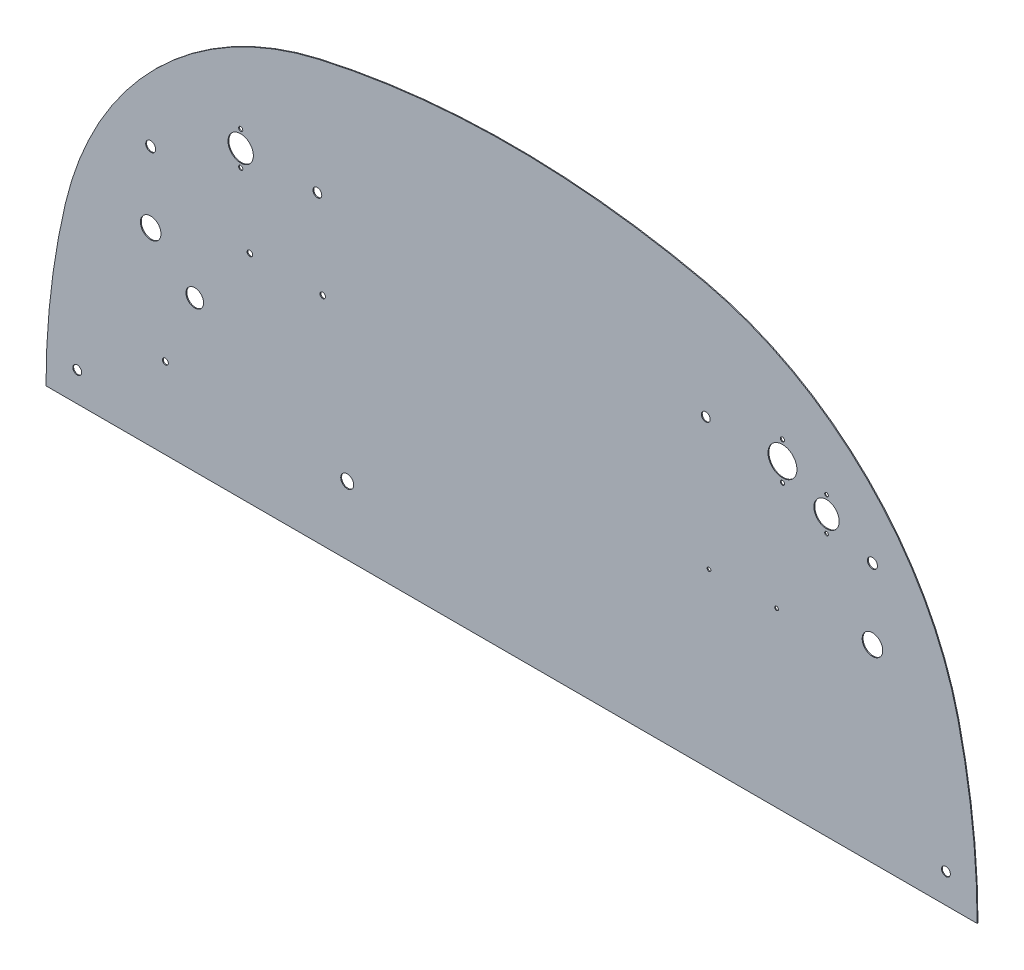
SolidWorks part; units mm, degrees
ref_plane "Front Plane" through (0, 0, 0) normal (0, 0, 1) x (1, 0, 0)
ref_plane "Top Plane" through (0, 0, 0) normal (0, 1, 0) x (1, 0, 0)
ref_plane "Right Plane" through (0, 0, 0) normal (1, 0, 0) x (0, 0, -1)
sketch "Base Sketch" plane through (0, 0, 0) normal (0, 0, 1) x (1, 0, 0)
  line L0 (0, 0) -> (750.8875, 0) construction
  line L1 (375.4437, 0) -> (375.4437, 236.5375) construction
  line L2 (543.3219, 236.5375) -> (207.5656, 236.5375) construction
  line L3 (-26.9875, -25.4) -> (777.875, -25.4)
  line L4 (375.4437, 0) -> (375.4437, -25.4) construction
  line L5 (375.4437, 236.5375) -> (375.4437, 355.6) construction
  line L6 (375.4437, 355.6) -> (-26.9875, 355.6) construction
  line L7 (-1.5875, -25.4) -> (375.4437, -25.4) construction
  line L8 (-1.5875, -25.4) -> (-1.5875, 152.4) construction
  line L9 (-1.5875, 152.4) -> (375.4437, 152.4) construction
  line L10 (375.4437, -25.4) -> (375.4437, 152.4) construction
  line L11 (23.8125, -25.4) -> (375.4437, -25.4) construction
  line L12 (23.8125, -25.4) -> (23.8125, 203.2) construction
  line L13 (23.8125, 203.2) -> (375.4437, 203.2) construction
  line L14 (375.4437, -25.4) -> (375.4437, 203.2) construction
  line L15 (49.2125, -25.4) -> (375.4437, -25.4) construction
  line L16 (49.2125, -25.4) -> (49.2125, 228.6) construction
  line L17 (49.2125, 228.6) -> (375.4437, 228.6) construction
  line L18 (375.4437, -25.4) -> (375.4437, 228.6) construction
  line L19 (74.6125, -25.4) -> (375.4437, -25.4) construction
  line L20 (74.6125, -25.4) -> (74.6125, 254) construction
  line L21 (74.6125, 254) -> (375.4437, 254) construction
  line L22 (375.4437, -25.4) -> (375.4437, 254) construction
  line L23 (100.0125, -25.4) -> (375.4437, -25.4) construction
  line L24 (100.0125, -25.4) -> (100.0125, 276.225) construction
  line L25 (100.0125, 276.225) -> (375.4437, 276.225) construction
  line L26 (375.4437, -25.4) -> (375.4437, 276.225) construction
  line L27 (125.4125, -25.4) -> (375.4437, -25.4) construction
  line L28 (125.4125, -25.4) -> (125.4125, 292.1) construction
  line L29 (125.4125, 292.1) -> (375.4437, 292.1) construction
  line L30 (375.4437, -25.4) -> (375.4437, 292.1) construction
  line L31 (150.8125, -25.4) -> (375.4437, -25.4) construction
  line L32 (150.8125, -25.4) -> (150.8125, 301.625) construction
  line L33 (150.8125, 301.625) -> (375.4437, 301.625) construction
  line L34 (375.4437, -25.4) -> (375.4437, 301.625) construction
  line L35 (176.2125, -25.4) -> (375.4437, -25.4) construction
  line L36 (176.2125, -25.4) -> (176.2125, 314.325) construction
  line L37 (176.2125, 314.325) -> (375.4437, 314.325) construction
  line L38 (375.4437, -25.4) -> (375.4437, 314.325) construction
  line L39 (201.6125, -25.4) -> (375.4437, -25.4) construction
  line L40 (201.6125, -25.4) -> (201.6125, 322.2625) construction
  line L41 (201.6125, 322.2625) -> (375.4437, 322.2625) construction
  line L42 (375.4437, -25.4) -> (375.4437, 322.2625) construction
  line L43 (227.0125, -25.4) -> (375.4437, -25.4) construction
  line L44 (227.0125, -25.4) -> (227.0125, 330.2) construction
  line L45 (227.0125, 330.2) -> (375.4437, 330.2) construction
  line L46 (375.4437, -25.4) -> (375.4437, 330.2) construction
  line L47 (252.4125, -25.4) -> (375.4437, -25.4) construction
  line L48 (252.4125, -25.4) -> (252.4125, 338.1375) construction
  line L49 (252.4125, 338.1375) -> (375.4437, 338.1375) construction
  line L50 (375.4437, -25.4) -> (375.4437, 338.1375) construction
  line L51 (277.8125, -25.4) -> (375.4437, -25.4) construction
  line L52 (277.8125, -25.4) -> (277.8125, 349.25) construction
  line L53 (277.8125, 349.25) -> (375.4437, 349.25) construction
  line L54 (375.4437, -25.4) -> (375.4437, 349.25) construction
  line L55 (-26.9875, -25.4) -> (-26.9875, 355.6) construction
  circle A0 centre (0, 0) radius 3.81
  circle A1 centre (750.8875, 0) radius 3.81
  circle A2 centre (207.5656, 236.5375) radius 3.81
  circle A3 centre (543.3219, 236.5375) radius 3.81
  arc A4 (-26.9875, -25.4) -> (777.875, -25.4) centre (375.4437, -47.434) cw construction
  arc A8 (-26.9875, -25.4) -> (-10.2771, 119.3168) centre (608.0125, -25.4) cw
  arc A9 (-10.2771, 119.3168) -> (208.9647, 336.9843) centre (273.2915, 52.9448) cw
  arc A10 (208.9647, 336.9843) -> (541.9228, 336.9843) centre (375.4437, -398.1152) cw
  arc A11 (761.1646, 119.3168) -> (541.9228, 336.9843) centre (477.596, 52.9448) ccw
  arc A12 (777.875, -25.4) -> (761.1646, 119.3168) centre (142.875, -25.4) ccw
  point P9 (375.4437, 236.5375)
  point P59 (0, 0)
  point P61 (0, 0)
  dimension "D1" = 7.62
  dimension "D2" = 750.8875
  dimension "D3" = 236.5375
  dimension "D4" = 335.7562
  dimension "D5" = 25.4
  dimension "D6" = 26.9875
  dimension "D8" = 25.4
  dimension "D9" = 177.8
  dimension "D10" = 50.8
  dimension "D11" = 228.6
  dimension "D12" = 76.2
  dimension "D13" = 254
  dimension "D14" = 101.6
  dimension "D15" = 279.4
  dimension "D16" = 127
  dimension "D17" = 301.625
  dimension "D18" = 152.4
  dimension "D19" = 317.5
  dimension "D20" = 177.8
  dimension "D21" = 327.025
  dimension "D22" = 203.2
  dimension "D23" = 339.725
  dimension "D24" = 228.6
  dimension "D25" = 347.6625
  dimension "D26" = 254
  dimension "D27" = 355.6
  dimension "D28" = 279.4
  dimension "D29" = 363.5375
  dimension "D30" = 304.8
  dimension "D31" = 374.65
extrude "Base w Mount Holes" add sketch "Base Sketch" along normal blind 0.7366
sketch "Throttle and Choke Cutout Sketch" plane through (0, 0, 0.7366) normal (0, 0, 1) x (1, 0, 0)
  line L0 (375.4438, -25.4) -> (375.4438, 355.6) construction
  line L2 (63.5, 199.0725) -> (63.5, 138.1125) construction
  line L3 (-26.9875, -25.4) -> (777.875, -25.4) construction
  line L4 (687.3875, 199.0725) -> (687.3875, 138.1125) construction
  circle A1 centre (63.5, 138.1125) radius 8.89
  circle A2 centre (63.5, 199.0725) radius 4.318
  arc A5 (541.9228, 336.9843) -> (208.9647, 336.9843) centre (375.4437, -398.1152) ccw construction
  circle A6 centre (687.3875, 199.0725) radius 4.318
  circle A7 centre (687.3875, 138.1125) radius 8.89
  point P11 (0, 0)
  dimension "D1" = 17.78
  dimension "D2" = 8.636
  dimension "D3" = 63.5
  dimension "D4" = 138.1125
  dimension "D5" = 199.0725
extrude "Throttle and Choke Cutouts" cut sketch "Throttle and Choke Cutout Sketch" against normal through all
sketch "Starter Relay Mount Sketch" plane through (0, 0, 0.7366) normal (0, 0, 1) x (1, 0, 0)
  line L0 (149.225, 161.925) -> (212.217, 161.925) construction
  circle A0 centre (149.225, 161.925) radius 2.3813
  circle A1 centre (212.217, 161.925) radius 2.3813
  dimension "D2" = 4.7625
  dimension "D1" = 62.992
  dimension "D3" = 149.225
  dimension "D4" = 161.925
extrude "Starter Relay Mount" cut sketch "Starter Relay Mount Sketch" against normal through all
sketch "Oil Pressure Sender Clamp Mount Sketch" plane through (0, 0, 0.7366) normal (0, 0, 1) x (1, 0, 0)
  circle A0 centre (76.2, 44.45) radius 2.54
  dimension "D1" = 5.08
  dimension "D2" = 76.2
  dimension "D3" = 44.45
extrude "Oil Pressure Sender Clamp Mount" cut sketch "Oil Pressure Sender Clamp Mount Sketch" against normal through all contours A0
sketch "Starter Power Cutout Sketch" plane through (0, 0, 0.7366) normal (0, 0, 1) x (1, 0, 0)
  circle A0 centre (233.3625, 33.3375) radius 5.588
  dimension "D1" = 11.176
  dimension "D2" = 233.3625
  dimension "D3" = 33.3375
extrude "Starter Power Cutout" cut sketch "Starter Power Cutout Sketch" against normal through all
sketch "Fuel Return Cutout Sketch" plane through (0, 0, 0.7366) normal (0, 0, 1) x (1, 0, 0)
  circle A0 centre (101.6, 104.775) radius 7.62
  dimension "D3" = 15.24
  dimension "D1" = 101.6
  dimension "D2" = 104.775
extrude "Fuel Return Cutout" cut sketch "Fuel Return Cutout Sketch" against normal through all
sketch "Brake Master Cyl Mount Sketch" plane through (0, 0, 0.7366) normal (0, 0, 1) x (1, 0, 0)
  line L0 (546.1, 123.825) -> (604.52, 123.825) construction
  circle A0 centre (546.1, 123.825) radius 1.6256
  circle A1 centre (604.52, 123.825) radius 1.6256
  dimension "D1" = 3.2512
  dimension "D2" = 546.1
  dimension "D3" = 123.825
  dimension "D4" = 58.42
extrude "Brake Master Cyl Mount" cut sketch "Brake Master Cyl Mount Sketch" against normal through all
sketch "Cutout - AS012 - Instrumentation Right Sketch" plane through (0, 0, 0.7366) normal (0, 0, 1) x (1, 0, 0)
  line L0 (141.2875, 221.9871) -> (141.2875, 236.5375) construction
  line L1 (141.2875, 236.5375) -> (141.2875, 251.0879) construction
  line L2 (207.5656, 236.5375) -> (543.3219, 236.5375) construction
  line L3 (141.2875, 236.5375) -> (207.5656, 236.5375) construction
  circle A0 centre (141.2875, 236.5375) radius 10.9499
  circle A1 centre (141.2875, 221.9871) radius 1.8034
  circle A2 centre (141.2875, 251.0879) radius 1.8034
  dimension "D1" = 21.8999
  dimension "D2" = 3.6068
  dimension "D3" = 29.1008
  dimension "D4" = 141.2875
extrude "Cutout - AS012 - Instrumentation Right" cut sketch "Cutout - AS012 - Instrumentation Right Sketch" against normal through all
sketch "Cutout - AS014 - Tach and CDI Enables Left Sketch" plane through (0, 0, 0.7366) normal (0, 0, 1) x (1, 0, 0)
  line L0 (609.6, 220.2878) -> (609.6, 236.5375) construction
  line L1 (609.6, 236.5375) -> (609.6, 252.7871) construction
  line L2 (609.6, 236.5375) -> (543.3219, 236.5375) construction
  circle A0 centre (609.6, 236.5375) radius 12.4968
  circle A1 centre (609.6, 252.7871) radius 1.8034
  circle A2 centre (609.6, 220.2878) radius 1.8034
  dimension "D2" = 3.6068
  dimension "D3" = 24.9936
  dimension "D1" = 32.4993
  dimension "D4" = 609.6
extrude "Cutout - AS014 - Tach and CDI Enables Left" cut sketch "Cutout - AS014 - Tach and CDI Enables Left Sketch" against normal through all
sketch "Cutout - AS012 - Instrumentation Left Sketch" plane through (0, 0, 0.7366) normal (0, 0, 1) x (1, 0, 0)
  line L0 (647.7, 201.3496) -> (647.7, 215.9) construction
  line L1 (647.7, 215.9) -> (647.7, 230.4504) construction
  circle A0 centre (647.7, 215.9) radius 10.9499
  circle A1 centre (647.7, 230.4504) radius 1.6002
  circle A2 centre (647.7, 201.3496) radius 1.6002
  dimension "D1" = 21.8999
  dimension "D2" = 3.2004
  dimension "D3" = 29.1008
  dimension "D4" = 647.7
  dimension "D5" = 215.9
extrude "Cutout - AS012 - Instrumentation Left" cut sketch "Cutout - AS012 - Instrumentation Left Sketch" against normal through all
